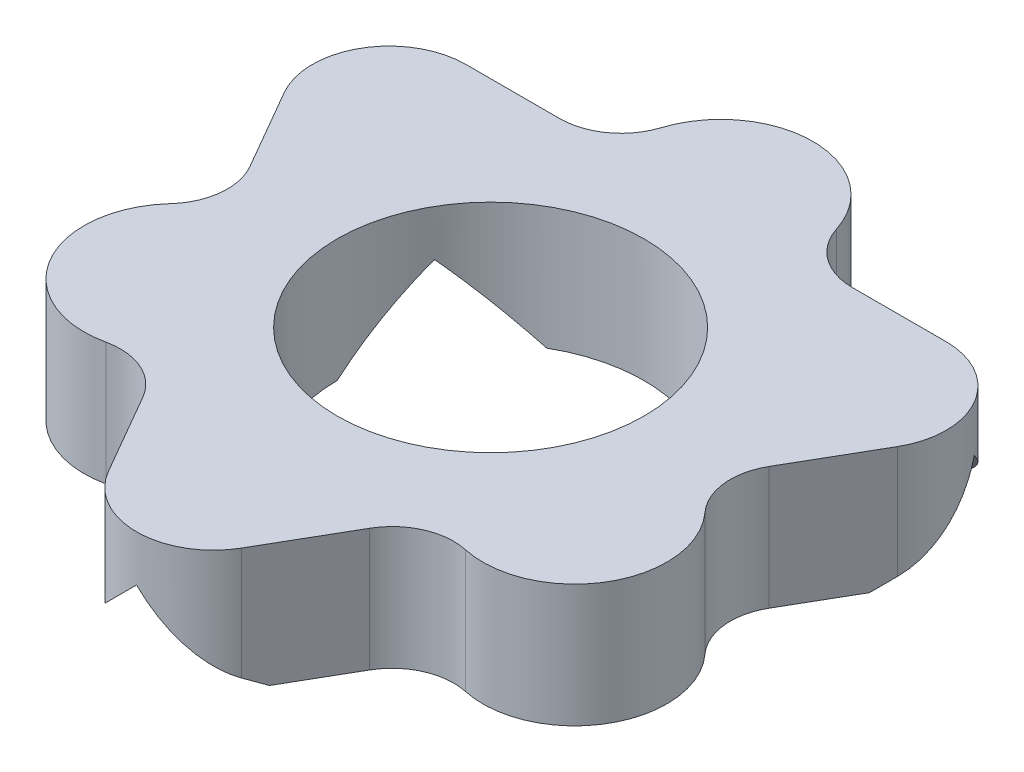
SolidWorks part; units mm, degrees
note: '?' marks a value the reader was unsure of.
material "Chrome Stainless Steel"
ref_plane "Front Plane" through (0, 0, 0) normal (0, 0, 1) x (1, 0, 0)
ref_plane "Top Plane" through (0, 0, 0) normal (0, 1, 0) x (1, 0, 0)
ref_plane "Right Plane" through (0, 0, 0) normal (1, 0, 0) x (0, 0, -1)
sketch "Sketch1" plane through (0, 0, 0) normal (0, 1, 0) x (1, 0, 0)
  line L0 (-3.8909, 3.147) -> (-2.3605, 0.4962)
  line L1 (8.2641, -10.4061) -> (9.7945, -7.7554)
  line L2 (13.9239, 6.897) -> (10.8631, 6.897)
  line L3 (-0.528, -3.9469) -> (15.4056, 5.2524) construction
  line L4 (6.099, 6.897) -> (6.099, -11.9869) construction
  line L5 (10.4292, -2.6207) -> (-3.7639, 5.5736) construction
  line L6 (2.4036, -7.7554) -> (3.934, -10.4061)
  line L7 (-6.056, 6.897) -> (3.1381, 6.897) construction
  line L8 (18.254, 6.897) -> (6.099, -14.1561) construction
  line L9 (6.099, -14.1561) -> (-6.056, 6.897) construction
  line L10 (-6.056, 6.897) -> (18.254, 6.897) construction
  line L11 (14.5586, 0.4962) -> (16.089, 3.147)
  line L12 (1.335, 6.897) -> (-1.7258, 6.897)
  line L13 (9.06, 6.897) -> (18.254, 6.897) construction
  circle A0 centre (6.099, -0.1207) radius 5
  circle A1 centre (6.099, -0.1207) radius 7.5 construction
  arc A2 (0.2445, -6.8015) -> (-2.614, -1.8505) centre (-0.3961, -3.8707) cw
  arc A3 (2.4036, -7.7554) -> (0.2445, -6.8015) centre (0.6715, -8.7554) ccw
  arc A4 (-3.8909, 3.147) -> (-1.7258, 6.897) centre (-1.7258, 4.397) cw
  arc A5 (8.2641, -10.4061) -> (3.934, -10.4061) centre (6.099, -9.1561) cw
  arc A6 (13.9239, 6.897) -> (16.089, 3.147) centre (13.9239, 4.397) cw
  arc A7 (-2.3605, 0.4962) -> (-2.614, -1.8505) centre (-4.0926, -0.5038) cw
  arc A8 (9.7945, -7.7554) -> (11.9536, -6.8015) centre (11.5265, -8.7554) cw
  arc A9 (14.8121, -1.8505) -> (11.9536, -6.8015) centre (12.5942, -3.8707) cw
  arc A10 (14.8121, -1.8505) -> (14.5586, 0.4962) centre (16.2906, -0.5038) cw
  arc A11 (3.2406, 8.2899) -> (8.9575, 8.2899) centre (6.099, 7.3793) cw
  arc A12 (1.335, 6.897) -> (3.2406, 8.2899) centre (1.335, 8.897) ccw
  arc A13 (10.8631, 6.897) -> (8.9575, 8.2899) centre (10.8631, 8.897) cw
  point P7 (-0.3961, -3.8707)
  point P8 (6.099, 7.3793)
  point P9 (-6.056, 6.897)
  point P10 (12.5942, -3.8707)
  point P12 (6.099, -14.1561)
  point P16 (6.099, -0.1207)
  point P30 (1.502, -6.1939)
  dimension "D1" = 10
  dimension "D5" = 15
  dimension "D6" = 2.5
  dimension "D7" = 3
  dimension "D8" = 2
  dimension "D9" = 2
  dimension "D10" = 3
  dimension "D11" = 2
  dimension "D12" = 3
  dimension "D2" = 120
  dimension "D3" = 240
  dimension "D4" = 24.31
extrude "Extrude1" add sketch "Sketch1" along normal blind 4
sketch "GrooveSketch" plane through (0, 0, 0) normal (0, 0, 1) x (1, 0, 0)
  line L0 (3.934, 4) -> (8.2641, 0) construction
  line L1 (8.2641, 4) -> (3.934, 0) construction
  line L2 (6.099, 0) -> (6.099, 2.5) construction
  line L3 (3.934, 0) -> (8.2641, 0) construction
  line L4 (6.099, 0) -> (0.2445, 0) construction
  line L5 (6.099, 0) -> (11.9536, 0) construction
  line L6 (6.099, 2.5) -> (3.599, 0)
  line L7 (6.099, 2.5) -> (8.599, 0)
  circle A0 centre (6.099, -0.8658) radius 2.38 construction
  dimension "D2" = 4.76
  dimension "D1" = 2.5
  dimension "D3" = 90
  dimension "D4" = 45
extrude "Extrude4" cut sketch "GrooveSketch" along normal up to next from surface
ref_axis "Axis1" through (6.099, 4, 0.1207) along (0, -1, 0)?
ref_plane "Plane1" through (4.6266, 0, 2.6711) normal (-0.866, 0, -0.5) x (-0.5, 0, 0.866)
ref_plane "Plane2" through (4.522, 0, -2.6108) normal (0.866, 0, -0.5) x (-0.5, 0, -0.866)
sketch "Sketch9" plane through (4.6266, 0, 2.6711) normal (-0.866, 0, -0.5) x (-0.5, 0, 0.866)
  line L2 (-2.945, 0) -> (-2.945, 2.5) construction
  line L3 (-2.945, 0) -> (-8.7995, 0) construction
  line L4 (-2.945, 0) -> (2.9096, 0) construction
  line L5 (-2.945, 2.5) -> (-5.445, 0)
  line L6 (-2.945, 2.5) -> (-0.445, 0)
  line L7 (-2.945, 4) -> (-2.945, 0) construction
  line L8 (-5.11, 0) -> (-0.7799, 0) construction
  circle A0 centre (-2.945, -0.8658) radius 2.38 construction
  dimension "D1" = 4.76
  dimension "D2" = 2.5
  dimension "D3" = 90
  dimension "D4" = 45
extrude "Extrude5" cut sketch "Sketch9" along normal through all from surface
sketch "Sketch10" plane through (4.522, 0, -2.6108) normal (0.866, 0, -0.5) x (-0.5, 0, -0.866)
  line L2 (-3.1541, 0) -> (-3.1541, 2.5) construction
  line L3 (-3.1541, 0) -> (13.4676, 0) construction
  line L4 (-3.1541, 0) -> (25.1768, 0) construction
  line L5 (-3.1541, 2.5) -> (-5.6541, 0)
  line L6 (-3.1541, 2.5) -> (-0.6541, 0)
  line L7 (-5.3191, 0) -> (-0.989, 0) construction
  line L8 (-3.1541, 4) -> (-3.1541, 0) construction
  circle A0 centre (-3.1541, -0.8658) radius 2.38 construction
  dimension "D1" = 4.76
  dimension "D2" = 2.5
  dimension "D3" = 90
  dimension "D4" = 45
extrude "Extrude6" cut sketch "Sketch10" along normal through all from surface
